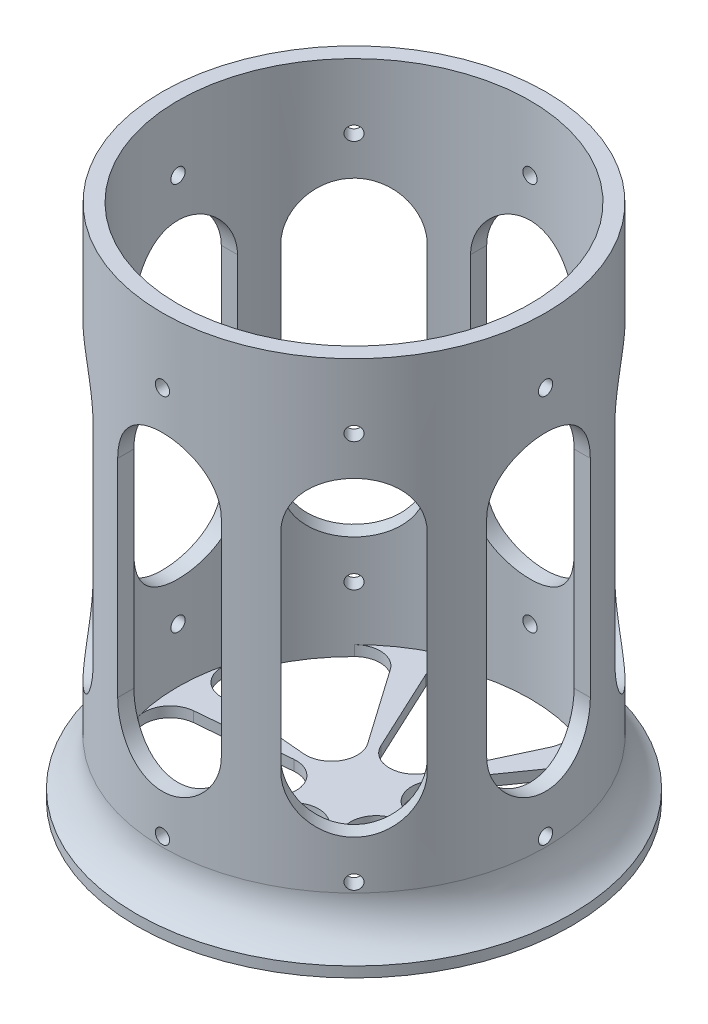
SolidWorks part; units mm, degrees
ref_plane "Front Plane" through (0, 0, 0) normal (0, 0, 1) x (1, 0, 0)
ref_plane "Top Plane" through (0, 0, 0) normal (0, 1, 0) x (1, 0, 0)
ref_plane "Right Plane" through (0, 0, 0) normal (1, 0, 0) x (0, 0, -1)
sketch "Body tube profile" plane through (0, 0, 0) normal (0, 1, 0) x (1, 0, 0)
  circle A0 centre (0, 0) radius 34
  dimension "D1" = 68
sketch "Sketch2" plane through (0, 0, 0) normal (0, 1, 0) x (1, 0, 0)
  circle A0 centre (0, 0) radius 34 construction
  circle A1 centre (0, 0) radius 34
  circle A2 centre (0, 0) radius 37
  dimension "D1" = 3
extrude "Main extrude" add sketch "Sketch2" along normal blind 100
sketch "Sketch3" plane through (0, 0, 0) normal (0, 0, 1) x (1, 0, 0)
  line L0 (-37, 0) -> (37, 0) construction
  line L1 (37, 100) -> (-37, 100) construction
  circle A0 centre (0, 12.5) radius 1.375
  circle A1 centre (0, 87.5) radius 1.375
  dimension "D1" = 2.75
  dimension "D3" = 2.75
  dimension "D2" = 12.5
  dimension "D4" = 12.5
extrude "Screwhole" cut sketch "Sketch3" along normal blind 100
sketch "Sketch4" plane through (0, 0, 0) normal (0, 0, 1) x (1, 0, 0)
  line L0 (0, 70) -> (0, 30) construction
  line L1 (10, 70) -> (10, 30)
  line L2 (-10, 70) -> (-10, 30)
  arc A0 (10, 70) -> (-10, 70) centre (0, 70) ccw
  arc A1 (-10, 30) -> (10, 30) centre (0, 30) ccw
  point P3 (0, 50)
  dimension "D3" = 10
  dimension "D1" = 50
  dimension "D2" = 40
extrude "Weight reduction" cut sketch "Sketch4" along normal blind 100
pattern_circular "Screwhole pattern" count 8 over 360 about axis through (0, 0, 0) along (0, 1, 0) of "Screwhole", "Weight reduction"
sketch "Sketch5" plane through (0, 0, 0) normal (0, -1, 0) x (1, 0, 0)
  line L0 (-4.5315, 9.7179) -> (-12.0724, 25.8893)
  line L1 (4.5315, 9.7179) -> (12.0724, 25.8893)
  line L2 (0, 0) -> (0, 34) construction
  line L3 (6.1502, 8.7834) -> (16.3846, 23.3997)
  line L4 (10.6817, 0.9345) -> (28.457, 2.4897)
  line L5 (10.6817, -0.9345) -> (28.457, -2.4897)
  line L6 (6.1502, -8.7834) -> (16.3846, -23.3997)
  line L7 (4.5315, -9.7179) -> (12.0724, -25.8893)
  line L8 (-4.5315, -9.7179) -> (-12.0724, -25.8893)
  line L9 (-6.1502, -8.7834) -> (-16.3846, -23.3997)
  line L10 (-10.6817, -0.9345) -> (-28.457, -2.4897)
  line L11 (-10.6817, 0.9345) -> (-28.457, 2.4897)
  line L12 (-6.1502, 8.7834) -> (-16.3846, 23.3997)
  arc A0 (8.841, 32.8304) -> (-8.841, 32.8304) centre (0, 0) ccw
  circle A1 centre (0, 0) radius 37
  circle A2 centre (0, 0) radius 37 construction
  circle A3 centre (0, 0) radius 34 construction
  arc A4 (-4.5315, 9.7179) -> (4.5315, 9.7179) centre (0, 11.831) ccw
  arc A5 (12.0724, 25.8893) -> (8.841, 32.8304) centre (7.5409, 28.0024) ccw
  arc A6 (-12.0724, 25.8893) -> (-8.841, 32.8304) centre (-7.5409, 28.0024) cw
  arc A7 (32.8525, 8.7587) -> (24.0115, 24.0717) centre (0, 0) ccw
  arc A8 (16.3846, 23.3997) -> (24.0115, 24.0717) centre (20.4804, 20.5318) cw
  arc A9 (28.457, 2.4897) -> (32.8525, 8.7587) centre (28.0212, 7.4706) ccw
  arc A10 (6.1502, 8.7834) -> (10.6817, 0.9345) centre (10.246, 5.9155) ccw
  arc A11 (24.0115, -24.0717) -> (32.8525, -8.7587) centre (0, 0) ccw
  arc A12 (28.457, -2.4897) -> (32.8525, -8.7587) centre (28.0212, -7.4706) cw
  arc A13 (16.3846, -23.3997) -> (24.0115, -24.0717) centre (20.4804, -20.5318) ccw
  arc A14 (10.6817, -0.9345) -> (6.1502, -8.7834) centre (10.246, -5.9155) ccw
  arc A15 (-8.841, -32.8304) -> (8.841, -32.8304) centre (0, 0) ccw
  arc A16 (12.0724, -25.8893) -> (8.841, -32.8304) centre (7.5409, -28.0024) cw
  arc A17 (-12.0724, -25.8893) -> (-8.841, -32.8304) centre (-7.5409, -28.0024) ccw
  arc A18 (4.5315, -9.7179) -> (-4.5315, -9.7179) centre (0, -11.831) ccw
  arc A19 (-32.8525, -8.7587) -> (-24.0115, -24.0717) centre (0, 0) ccw
  arc A20 (-16.3846, -23.3997) -> (-24.0115, -24.0717) centre (-20.4804, -20.5318) cw
  arc A21 (-28.457, -2.4897) -> (-32.8525, -8.7587) centre (-28.0212, -7.4706) ccw
  arc A22 (-6.1502, -8.7834) -> (-10.6817, -0.9345) centre (-10.246, -5.9155) ccw
  arc A23 (-24.0115, 24.0717) -> (-32.8525, 8.7587) centre (0, 0) ccw
  arc A24 (-28.457, 2.4897) -> (-32.8525, 8.7587) centre (-28.0212, 7.4706) cw
  arc A25 (-16.3846, 23.3997) -> (-24.0115, 24.0717) centre (-20.4804, 20.5318) ccw
  arc A26 (-10.6817, 0.9345) -> (-6.1502, 8.7834) centre (-10.246, 5.9155) ccw
  circle A27 centre (0, 0) radius 42
  point P63 (0, 0)
  dimension "D5" = 5
  dimension "D3" = 25
  dimension "D4" = 25
  dimension "D1" = 0
  dimension "D2" = 3
  dimension "D7" = 5
  dimension "D6" = 6
extrude "Plate for better adhesion" add sketch "Sketch5" against normal blind 2
fillet "Fillet1" radius 10 1 edges at (0, 2, -37)
